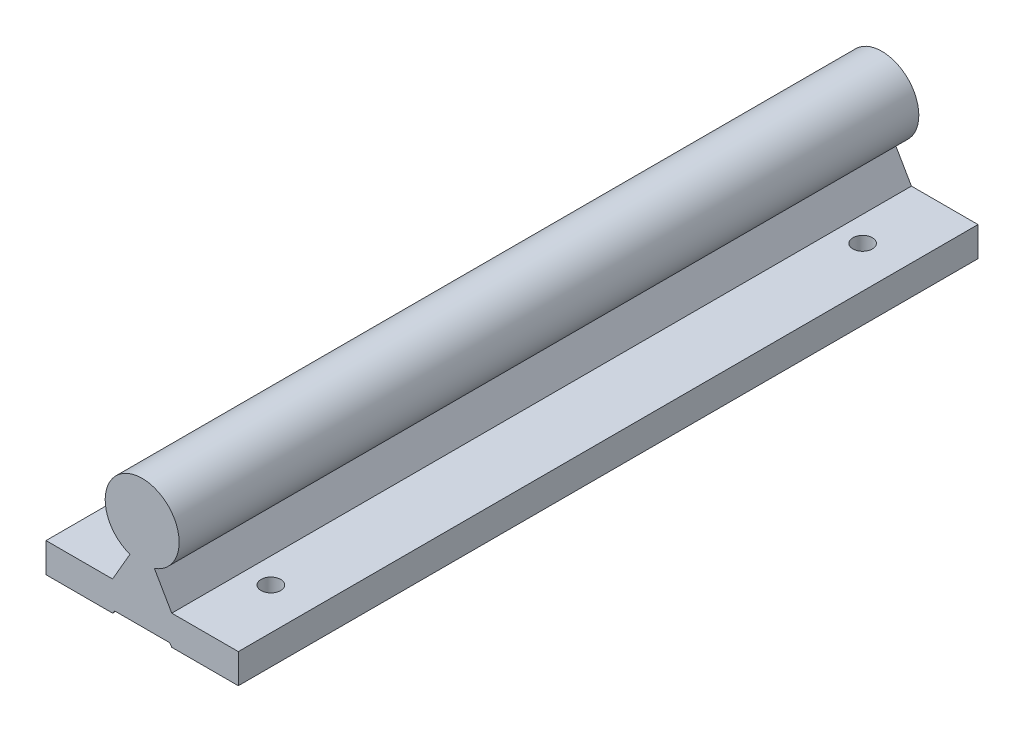
SolidWorks part; units mm, degrees
ref_plane "Спереди" through (0, 0, 0) normal (0, 0, 1) x (1, 0, 0)
ref_plane "Сверху" through (0, 0, 0) normal (0, 1, 0) x (1, 0, 0)
ref_plane "Справа" through (0, 0, 0) normal (1, 0, 0) x (0, 0, -1)
sketch "Эскиз2" plane through (0, 0, 0) normal (0, 0, 1) x (1, 0, 0)
  line L0 (4.1277, -11.7988) -> (10, -21.97)
  line L1 (10, -21.97) -> (32.5, -21.97)
  line L2 (32.5, -21.97) -> (32.5, -31.97)
  line L3 (32.5, -31.97) -> (10, -31.97)
  line L4 (10, -31.97) -> (9.2998, -30.97)
  line L5 (9.2998, -30.97) -> (-9.2998, -30.97)
  line L6 (0, 0) -> (0, -47.3153) construction
  line L7 (-10, -31.97) -> (-9.2998, -30.97)
  line L8 (-32.5, -31.97) -> (-10, -31.97)
  line L9 (-32.5, -21.97) -> (-32.5, -31.97)
  line L10 (-10, -21.97) -> (-32.5, -21.97)
  line L11 (-4.1277, -11.7988) -> (-10, -21.97)
  line L12 (-10, -21.97) -> (-10, -30.191) construction
  circle A0 centre (0, 0) radius 12.5
  point P12 (0, -30.97)
  dimension "D6" = 25
  dimension "D1" = 10
  dimension "D2" = 60
  dimension "D3" = 20
  dimension "D4" = 65
  dimension "D5" = 31.97
  dimension "D8" = 1
  dimension "D9" = 70
extrude "Бобышка-Вытянуть2" add sketch "Эскиз2" along normal blind 250 contours A0
extrude "Бобышка-Вытянуть3" add sketch "Эскиз2<4>" along normal blind 250 contours A0 L6 L5 L4 L3 L2 L1 L0 | L6 A0 L11 L10 L9 L8 L7 L5 region at (0, -25.1827, 0)
sketch "Эскиз2<4>" plane through (0, 0, 0) normal (0, 0, 1) x (1, 0, 0) same geometry as "Эскиз2"
sketch "Эскиз7" plane through (0, -21.97, 0) normal (0, 1, 0) x (1, 0, 0)
  line L0 (0, -999.7956) -> (0, 51.3021) construction
  line L1 (-10, -250) -> (-32.5, -250) construction
  line L2 (-18.5, -225) -> (-32.5, -225) construction
  line L3 (-32.5, -250) -> (-32.5, 0) construction
  line L4 (18.5, -225) -> (32.5, -225) construction
  line L5 (32.5, -250) -> (32.5, 0) construction
  line L6 (18.5, -225) -> (18.5, 35.3486) construction
  line L8 (-18.5, -225) -> (-18.5, -44.837) construction
  line L11 (-32.5, -250) -> (-32.5, 0) construction
  line L12 (32.5, -250) -> (32.5, 0) construction
  circle A0 centre (-18.5, -225) radius 3.3
  circle A1 centre (18.5, -225) radius 3.3
  circle A2 centre (18.5, -25) radius 3.3
  circle A3 centre (-18.5, -25) radius 3.3
  point P7 (-21.25, -250)
  dimension "D1" = 25
  dimension "D2" = 37
  dimension "D3" = 6.6
  dimension "D4" = 200
  dimension "D5" = 37
extrude "Вырез-Вытянуть1" cut sketch "Эскиз7" against normal through all contours A1 | A0 | A3 | A2
hole_wizard "Цековка для винта с внутренним шестигранником M51" positions "Эскиз13" profile "Эскиз12" counterbore size "M5" standard "Ansi Metric"
sketch "Эскиз13" plane through (0, -30.97, 0) normal (0, -1, 0) x (-1, 0, 0)
  line L0 (-18.5, -225) -> (18.5, -225) construction
  line L2 (-18.5, -25) -> (18.5, -25) construction
  point P0 (0, -25)
  point P2 (0, -225)
sketch "Эскиз12" plane through (0, -30.97, 25) normal (1, 0, 0) x (0, 0, -1)
  line L0 (0, 0) -> (0, 19.5923)
  line L1 (0, 19.5923) -> (2.65, 18)
  line L2 (2.65, 18) -> (2.65, 5)
  line L3 (2.65, 5) -> (5, 5)
  line L4 (5, 5) -> (5, 0)
  line L5 (5, 0) -> (0, 0)
  line L10 (0, 19.5923) -> (-2.65, 18) construction
  line L11 (0, -6.35) -> (0, 107.95) construction
  dimension "Диаметр отверстия" = 5.3
  dimension "Глубина отверстия" = 18
  dimension "Диаметр цековки" = 10
  dimension "Глубина цековки" = 5
  dimension "Угол заточки сверла" = 118
equation "\"D\"=4.86916"
